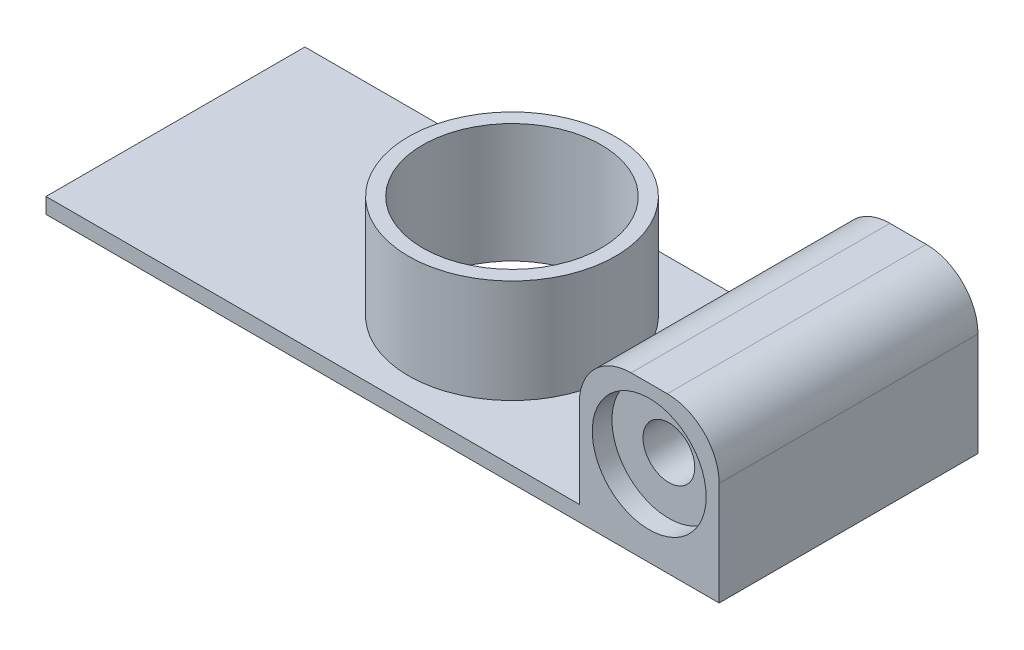
SolidWorks part; units mm, degrees
ref_plane "Front Plane" through (0, 0, 0) normal (0, 0, 1) x (1, 0, 0)
ref_plane "Top Plane" through (0, 0, 0) normal (0, 1, 0) x (1, 0, 0)
ref_plane "Right Plane" through (0, 0, 0) normal (1, 0, 0) x (0, 0, -1)
sketch "Sketch1" plane through (0, 0, 0) normal (0, 1, 0) x (1, 0, 0)
  line L1 (-65, 25) -> (65, 25)
  line L2 (-65, 25) -> (-65, -25)
  line L3 (-65, -25) -> (65, -25)
  line L4 (65, 25) -> (65, -25)
  line L5 (-65, 25) -> (65, -25) construction
  line L6 (-65, -25) -> (65, 25) construction
  point P0 (0, 0)
  dimension "D1" = 130
  dimension "D2" = 50
extrude "Boss-Extrude2" add sketch "Sketch1" along normal blind 6
sketch "Sketch5" plane through (0, 6, 0) normal (0, 1, 0) x (1, 0, 0)
  line L0 (65, 25) -> (-65, 25) construction
  line L1 (38, 25) -> (65, 25)
  line L2 (38, 25) -> (38, -25)
  line L3 (38, -25) -> (65, -25)
  line L4 (65, 25) -> (65, -25)
  line L5 (-65, -25) -> (65, -25) construction
  line L6 (65, -25) -> (65, 25) construction
  dimension "D1" = 27
extrude "Boss-Extrude4" add sketch "Sketch5" along normal blind 27
sketch "Sketch6" plane through (0, 0, 25) normal (0, 0, 1) x (1, 0, 0)
  line L0 (51.5, 33) -> (51.5, 0) construction
  line L1 (38, 33) -> (65, 33) construction
  line L2 (-65, 0) -> (65, 0) construction
  line L3 (38, 19.5) -> (65, 19.5)
  line L4 (38, 33) -> (38, 6) construction
  line L5 (65, 33) -> (65, 0) construction
  circle A0 centre (51.5, 19.5) radius 11
  circle A1 centre (51.5, 19.5) radius 5.5
  dimension "D1" = 22
  dimension "D2" = 11
extrude "Cut-Extrude3" cut sketch "Sketch6" against normal blind 3.8 contours A0
sketch "Sketch8" plane through (0, 0, 21.2) normal (0, 0, 1) x (1, 0, 0)
  circle A0 centre (51.5, 19.5) radius 5
  dimension "D1" = 10
extrude "Cut-Extrude4" cut sketch "Sketch8" against normal blind 12
sketch "Sketch9" plane through (0, 0, -25) normal (0, 0, -1) x (-1, 0, 0)
  line L0 (-51.5, 33) -> (-51.5, 0) construction
  line L1 (-65, 33) -> (-38, 33) construction
  line L2 (-65, 0) -> (65, 0) construction
  line L3 (-38, 19.5) -> (-65, 19.5) construction
  line L4 (-38, 33) -> (-38, 6) construction
  line L5 (-65, 33) -> (-65, 0) construction
  circle A0 centre (-51.5, 19.5) radius 11
  dimension "D1" = 22
extrude "Cut-Extrude5" cut sketch "Sketch9" against normal blind 3.8
sketch "Sketch10" plane through (0, 0, -21.2) normal (0, 0, -1) x (-1, 0, 0)
  circle A0 centre (-51.5, 19.5) radius 5
  dimension "D1" = 10
extrude "Cut-Extrude6" cut sketch "Sketch10" against normal blind 12.5
fillet "Fillet1" radius 10 1 edges at (38, 33, 0)
fillet "Fillet2" radius 10 1 edges at (65, 33, 0)
sketch "Sketch11" plane through (0, 6, 0) normal (0, 1, 0) x (1, 0, 0)
  line L0 (-65, 0) -> (0, 0) construction
  line L1 (-65, 25) -> (-65, -25) construction
sketch "Sketch12" plane through (0, 6, 0) normal (0, 1, 0) x (1, 0, 0)
  circle A0 centre (0, 0) radius 20
  dimension "D1" = 40
sketch "Sketch13" plane through (0, 0, -21.2) normal (0, 0, -1) x (-1, 0, 0)
extrude "Cut-Extrude7" cut sketch "Sketch10<2>" against normal blind 90
sketch "Sketch10<2>" plane through (0, 0, -21.2) normal (0, 0, -1) x (-1, 0, 0) same geometry as "Sketch10"
sketch "Sketch14" plane through (0, 6, 0) normal (0, 1, 0) x (1, 0, 0)
  circle A1 centre (0, 0) radius 20
  dimension "D1" = 40
extrude "Boss-Extrude5" add sketch "Sketch14" along normal blind 20
sketch "Sketch15" plane through (0, 26, 0) normal (0, 1, 0) x (1, 0, 0)
  circle A0 centre (0, 0) radius 17.25
  dimension "D1" = 34.5
extrude "Cut-Extrude8" cut sketch "Sketch15" against normal blind 60
sketch "Sketch16" plane through (0, 0, 0) normal (0, -1, 0) x (1, 0, 0)
  line L1 (-65, 25) -> (65, 25)
  line L2 (-65, 25) -> (-65, -25)
  line L3 (-65, -25) -> (65, -25)
  line L4 (65, 25) -> (65, -25)
extrude "Cut-Extrude9" cut sketch "Sketch16" against normal blind 3
